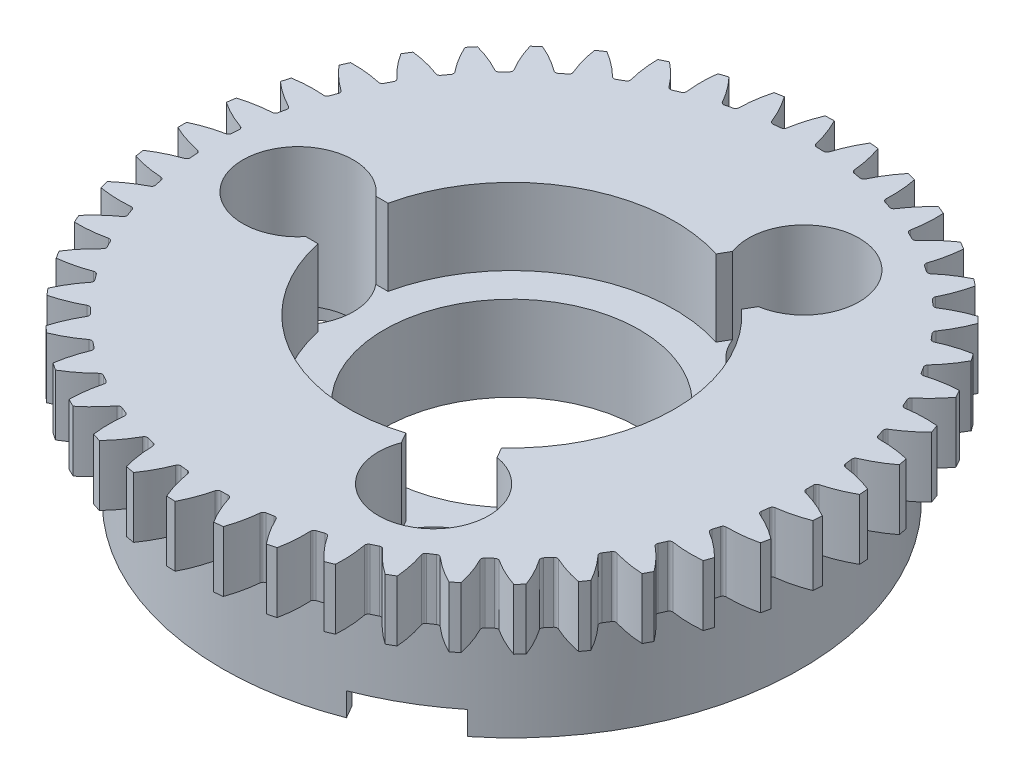
SolidWorks part; units mm, degrees
ref_plane "Front Plane" through (0, 0, 0) normal (0, 0, 1) x (1, 0, 0)
ref_plane "Top Plane" through (0, 0, 0) normal (0, 1, 0) x (1, 0, 0)
ref_plane "Right Plane" through (0, 0, 0) normal (1, 0, 0) x (0, 0, -1)
sketch "Sketch2" plane through (0, 0, 0) normal (0, 1, 0) x (1, 0, 0)
  circle A0 centre (0, 0) radius 26.56
  circle A1 centre (-19.0525, 0) radius 4.926
  circle A2 centre (9.5262, 16.4999) radius 4.926
  circle A3 centre (9.5262, -16.4999) radius 4.926
  circle A5 centre (0, 0) radius 11.375
  point P2 (0, 0)
  point P11 (0, 0)
  point P12 (13.6656, 4.178)
  dimension "D2" = 3
  dimension "D1" = 22.75
  dimension "D4" = 53.12
  dimension "D5" = 9.852
  dimension "D3" = 19.0525
extrude "Boss-Extrude2" add sketch "Sketch2" along normal blind 5.4
sketch "Sketch4" plane through (0, 0, 0) normal (0, -1, 0) x (1, 0, 0)
  circle A0 centre (9.5262, 16.4999) radius 4.926 construction
  circle A1 centre (9.5262, 16.4999) radius 4.926
  circle A2 centre (0, 0) radius 9.625
  circle A19 centre (0, 0) radius 25.815
  point P6 (-1.3086, -0.0126)
  point P13 (12.187, -21.1085)
  point P15 (-24.374, 0)
  point P17 (12.187, 21.1085)
  point P18 (-12.5475, 0)
  point P25 (16.9495, -21.1085)
  point P26 (16.9495, 21.1085)
  point P27 (-26.7552, 4.1244)
  point P28 (9.8057, 25.2329)
  point P29 (9.8057, -25.2329)
  point P30 (-26.7552, -4.1244)
  point P31 (16.4175, -16.723)
  point P36 (16.4175, 16.723)
  point P46 (13.9118, 4.2533)
  circle M1 centre (9.5262, -16.4999) radius 4.926
  circle M2 centre (-19.0525, 0) radius 4.926
  circle M4 centre (0, 0) radius 11.375
  circle M5 centre (9.5262, 16.4999) radius 4.926
  dimension "D1" = 19.25
extrude "Boss-Extrude3" add sketch "Sketch4" along normal blind 8.98 contours A19 M1 M5 M4 M2 region at (-25.0848, 0, 0)
sketch "Sketch7" plane through (0, 5.4, 0) normal (0, 1, 0) x (1, 0, 0)
  line L0 (0, 0) -> (9.5262, 16.4999) construction
  line L1 (9.7843, -10.7013) -> (10.3258, -11.6393)
  line L2 (9.7843, 10.7013) -> (10.3258, 11.6393)
  line L4 (4.3755, -13.8241) -> (4.917, -14.762)
  line L5 (-14.1597, -3.1228) -> (-15.2428, -3.1228)
  line L6 (-14.1597, 3.1228) -> (-15.2428, 3.1228)
  line L7 (4.3755, 13.8241) -> (4.917, 14.762)
  arc A0 (4.3755, 13.8241) -> (-14.1597, 3.1228) centre (0, 0) ccw
  arc A1 (10.3258, -11.6393) -> (4.917, -14.762) centre (9.5262, -16.4999) ccw
  arc A2 (-15.2428, -3.1228) -> (-15.2428, 3.1228) centre (-19.0525, 0) ccw
  circle A4 centre (9.5262, 16.4999) radius 4.926 construction
  arc A5 (4.917, 14.762) -> (10.3258, 11.6393) centre (9.5262, 16.4999) ccw
  arc A6 (-14.1597, -3.1228) -> (4.3755, -13.8241) centre (0, 0) ccw
  arc A8 (9.7843, -10.7013) -> (9.7843, 10.7013) centre (0, 0) ccw
  point P21 (0, 0)
  point P28 (0, 0)
  point P29 (0, 0)
  dimension "D1" = 29
  dimension "D2" = 3
extrude "Cut-Extrude7" cut sketch "Sketch7" against normal blind 6.808
sketch "Sketch10" plane through (0, 5.4, 0) normal (0, 1, 0) x (1, 0, 0)
  circle A3 centre (0, 0) radius 25.56
  circle A4 centre (0, 0) radius 25.56
  dimension "D1" = 1
sketch "Sketch12" plane through (0, 5.4, 0) normal (0, 1, 0) x (1, 0, 0)
  line L0 (0, 0) -> (15.065, -26.0933) construction
  line L1 (13.28, -23.0016) -> (14.4058, -22.3516) construction
  arc A0 (11.9245, -23.7327) -> (14.5908, -22.1933) centre (0, 0) ccw
  circle A1 centre (0, 0) radius 26.56 construction
  circle A2 centre (0, 0) radius 29.38
  arc A3 (14.5908, -22.1933) -> (14.4715, -22.5401) centre (14.7557, -22.4439) ccw
  circle A4 centre (0, 0) radius 26.56 construction
  arc A5 (15.029, -25.2451) -> (14.4715, -22.5401) centre (3.8151, -26.1463) ccw
  arc A6 (14.3484, -25.638) -> (12.2846, -23.8027) centre (20.7358, -16.3771) cw
  arc A7 (11.9245, -23.7327) -> (12.2846, -23.8027) centre (12.0592, -24.0007) cw
  point P18 (25.3995, 7.7654)
  circle M13 centre (0, 0) radius 26.56
  dimension "D1" = 0.3
  dimension "D2" = 58.76
  dimension "D3" = 30.13
  dimension "D4" = 1.3
  dimension "D5" = 11.25
extrude "Boss-Extrude4" add sketch "Sketch12" against normal up to surface (5.4 mm away) contours A7 A6 A2 A5 A3 M13 region at (13.8631, 5.4, 24.0116) up to face at (0, 0, 26.56)
pattern_circular "CirPattern2" count 45 over 360 about axis through (0, 5.4, 0) along (0, 1, 0) of "Boss-Extrude4"
sketch "Sketch9" plane through (0, -8.98, 0) normal (0, -1, 0) x (1, 0, 0)
  line L0 (9.5262, -16.4999) -> (0, 0) construction
  line L1 (8.6529, -22.8905) -> (9.3331, -24.0688)
  line L2 (15.4974, -18.9389) -> (16.1776, -20.1171)
  line L3 (-24.1502, 3.9517) -> (-25.5108, 3.9517)
  line L4 (-24.1502, -3.9517) -> (-25.5108, -3.9517)
  line L5 (15.4974, 18.9389) -> (16.1776, 20.1171)
  line L6 (8.6529, 22.8905) -> (9.3331, 24.0688)
  arc A2 (-24.1502, -3.9517) -> (-24.1502, 3.9517) centre (-19.0525, 0) ccw
  arc A3 (15.9762, -16.4999) -> (15.9762, -16.4999) centre (9.5262, -16.4999) ccw
  arc A4 (15.4974, -18.9389) -> (8.6529, -22.8905) centre (9.5262, -16.4999) ccw
  arc A5 (-25.5108, 3.9517) -> (-25.5108, -3.9517) centre (0, 0) ccw
  circle A6 centre (0, 0) radius 25.815 construction
  arc A7 (9.3331, -24.0688) -> (16.1776, -20.1171) centre (0, 0) ccw
  arc A8 (8.6529, 22.8905) -> (15.4974, 18.9389) centre (9.5263, 16.4999) ccw
  arc A9 (16.1776, 20.1171) -> (9.3331, 24.0688) centre (0, 0) ccw
  point P9 (0, 0)
  point P22 (0, 0)
  dimension "D1" = 1.524
  dimension "D2" = 3
extrude "Cut-Extrude8" cut sketch "Sketch9" against normal blind 2.0875
